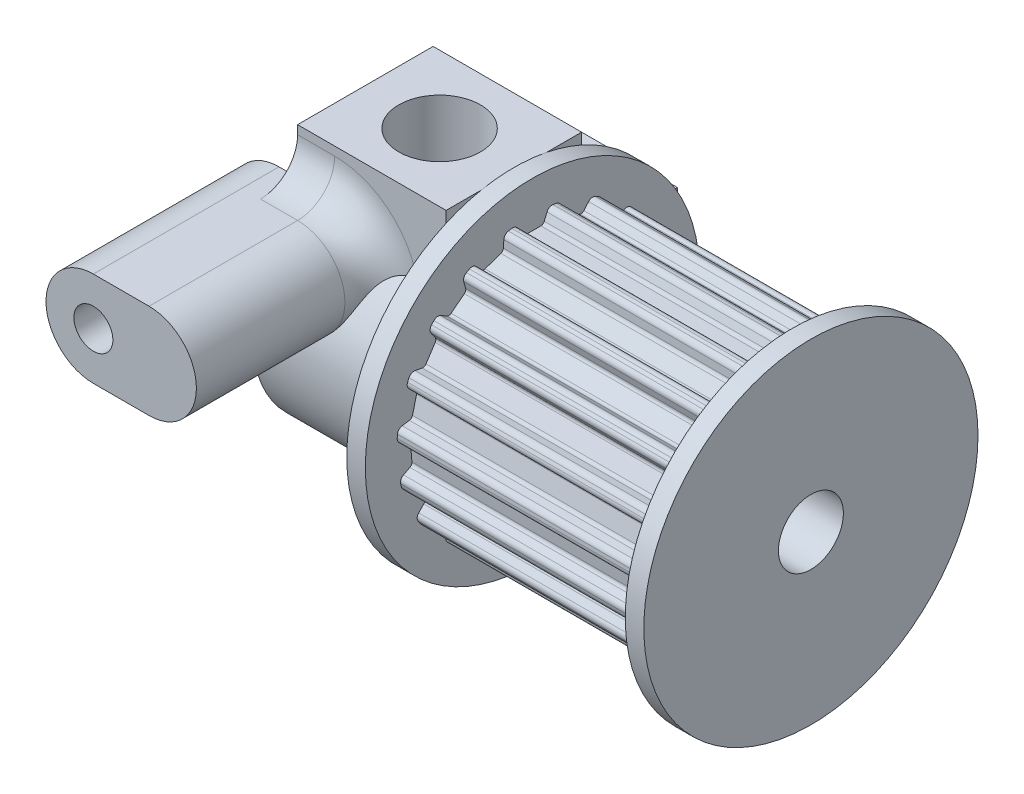
SolidWorks part; units mm, degrees
material "PLA Black"
ref_plane "Front" through (0, 0, 0) normal (0, 0, 1) x (1, 0, 0)
ref_plane "Top" through (0, 0, 0) normal (0, 1, 0) x (1, 0, 0)
ref_plane "Right" through (0, 0, 0) normal (1, 0, 0) x (0, 0, -1)
sketch "Sketch1" plane through (0, 0, 0) normal (1, 0, 0) x (0, 0, -1)
  line L0 (1.118, 1) -> (-1.118, 1) construction
  line L1 (-3.65, 4.8249) -> (3.65, 4.8249)
  line L2 (4.8249, 3.65) -> (4.8249, -3.65)
  line L3 (0, 0) -> (11.6334, 0) construction
  line L4 (0, 0) -> (0, 8.6732) construction
  arc A0 (-1.118, 1) -> (1.118, 1) centre (0, 0) ccw construction
  circle A1 centre (0, 0) radius 1.75
  arc A2 (4.8249, -3.65) -> (-3.65, 4.8249) centre (0, 0) cw
  arc A3 (4.8249, 3.65) -> (3.65, 4.8249) centre (0, 0) ccw
  dimension "D1" = 3
  dimension "D3" = 0.25
  dimension "D5" = 6.05
  dimension "D2" = 1
  dimension "D4" = 7.3
extrude "Boss-Extrude1" add sketch "Sketch1" along normal mid plane 8
sketch "Sketch2" plane through (0, 4.8249, 0) normal (0, 1, 0) x (1, 0, 0)
  circle A0 centre (0, 0) radius 2.2
  dimension "D1" = 4.4
extrude "Cut-Extrude1" cut sketch "Sketch2" against normal blind 5
sketch "Sketch7" plane through (4, 0, 0) normal (1, 0, 0) x (0, 0, -1)
  circle A0 centre (0, 0) radius 1.75 construction
  circle A1 centre (0, 0) radius 7.3
  circle A2 centre (0, 0) radius 1.75
  dimension "D1" = 14.6
extrude "Boss-Extrude5" add sketch "Sketch7" along normal blind 15
sketch "Sketch8" plane through (19, 0, 0) normal (1, 0, 0) x (0, 0, -1)
  line L0 (-0.4541, 6.5499) -> (0.4528, 6.5499)
  line L1 (0.6374, 6.6734) -> (0.7865, 7.0333)
  line L2 (-0.6389, 6.6734) -> (-0.788, 7.0333)
  line L6 (0, 9.2013) -> (0, 0) construction
  arc A0 (0.4528, 6.5499) -> (0.6374, 6.6734) centre (0.4526, 6.7499) ccw
  arc A1 (-0.4541, 6.5499) -> (-0.6389, 6.6734) centre (-0.4541, 6.7499) cw
  arc A2 (0.7865, 7.0333) -> (1.1093, 7.2152) centre (1.0638, 6.9187) cw
  arc A3 (-0.788, 7.0333) -> (-1.1108, 7.215) centre (-1.0652, 6.9185) ccw
  circle A4 centre (0, 0) radius 7.3 construction
  arc A5 (-1.1108, 7.215) -> (1.1093, 7.2152) centre (0, 0) cw
  point P3 (-0.0007, 6.5499)
  point P15 (0, 9.84)
extrude "Cut-Extrude3" cut sketch "Sketch8" against normal up to surface (15 mm away) up to face at (4, 0, -7.3)
pattern_circular "CirPattern1" count 19 over 360 about axis through (19, 0, 0) along (-1, 0, 0) of "Cut-Extrude3"
sketch "Sketch9" plane through (19, 0, 0) normal (1, 0, 0) x (0, 0, -1)
  circle A0 centre (0, 0) radius 9
  circle A1 centre (0, 0) radius 1.75 construction
  circle A2 centre (0, 0) radius 1.75
  dimension "D1" = 18
extrude "Boss-Extrude6" add sketch "Sketch9" along normal blind 1
sketch "Sketch10" plane through (4, 0, 0) normal (-1, 0, 0) x (0, 0, 1)
  circle A0 centre (0, 0) radius 9
  circle A1 centre (0, 0) radius 9 construction
  circle A2 centre (0, 0) radius 1.75 construction
  circle A3 centre (0, 0) radius 1.75
extrude "Boss-Extrude7" add sketch "Sketch10" against normal blind 1
sketch "Sketch3" plane through (0, 0, -4.8249) normal (0, 0, -1) x (-1, 0, 0)
  circle A0 centre (0, 0) radius 2.2
  dimension "D1" = 4.4
extrude "Cut-Extrude2" cut sketch "Sketch3" against normal blind 5
sketch "Sketch4" plane through (0, 4.8249, 0) normal (0, 1, 0) x (1, 0, 0)
  line L0 (4, 3.65) -> (-4, 3.65) construction
  line L2 (4, -3.65) -> (-4, -3.65) construction
  line L3 (-4, 3.65) -> (-4, -3.65) construction
  line L4 (4, 3.65) -> (-4, 3.65)
  line L5 (4, 3.65) -> (4, -3.65)
  line L6 (4, -3.65) -> (-4, -3.65)
  line L7 (-4, 3.65) -> (-4, -3.65)
  line L8 (4, 7.3) -> (4, -7.3) construction
  circle A0 centre (0, 0) radius 2.2 construction
  circle A1 centre (0, 0) radius 2.2
extrude "Boss-Extrude2" add sketch "Sketch4" along normal blind 4
sketch "Sketch5" plane through (0, 0, -4.8249) normal (0, 0, -1) x (-1, 0, 0)
  line L0 (-4, 3.65) -> (4, 3.65) construction
  line L1 (4, -3.65) -> (4, 3.65) construction
  line L2 (-4, -3.65) -> (4, -3.65) construction
  line L4 (-4, 3.65) -> (4, 3.65)
  line L5 (4, -3.65) -> (4, 3.65)
  line L6 (-4, -3.65) -> (4, -3.65)
  line L7 (-4, -3.65) -> (-4, 3.65)
  line L8 (-4, -7.3) -> (-4, 7.3) construction
  circle A0 centre (0, 0) radius 2.2 construction
  circle A1 centre (0, 0) radius 2.2
extrude "Boss-Extrude3" add sketch "Sketch5" along normal blind 4
ref_axis "Axis1" through (20, 0, 0) along (-1, 0, 0)
sketch "Sketch6" plane through (0, 0, 3.65) normal (0, 0, 1) x (1, 0, 0)
  line L0 (-4, 8.8249) -> (-4, 4.8249) construction
  line L2 (-2, 6.3555) -> (-5, 6.3555)
  line L3 (-5, 1.2545) -> (-2, 1.2545)
  line L6 (20, 0) -> (-4, 0) construction
  circle A0 centre (-5, 3.805) radius 1.0505
  arc A1 (-5, 6.3555) -> (-5, 1.2545) centre (-5, 3.805) ccw
  arc A2 (-2, 6.3555) -> (-2, 1.2545) centre (-2, 3.805) cw
  dimension "D1" = 2.101
  dimension "D2" = 3.805
  dimension "D3" = 1.5
  dimension "D4" = 1
  dimension "D5" = 3
extrude "Boss-Extrude4" add sketch "Sketch6" along normal blind 10
fillet "Fillet1" radius 2 2 edges at (-0.6029, 5.9388, 3.65) (-3, 6.3555, 3.65)
equation "\"knee_angle\"= 70"
equation "\"ankle_angle\" = 80"
equation "\"hip_angle\" = 40"
equation "\"spring_ankle_parallel_arm_diameter\"= 1.1"
equation "\"spring_ankle_parallel_arm_length\"= 13"
equation "\"spring_ankle_parallel_intern_diameter\"= 5.7"
equation "\"spring_ankle_parallel_angle\"= \"ankle_angle\""
equation "\"spring_ankle_parallel_turns\"= 3"
equation "\"spring_ankle_parallel_pitch\"= \"spring_ankle_parallel_arm_diameter\" * 1.01"
equation "\"spring_ankle_parallel_cutting_distance\"= (1-\"spring_ankle_parallel_angle\" / 360) * \"spring_ankle_parallel_pitch\""
equation "\"spring_ankle_serial_arm_diameter\"= 1.91"
equation "\"spring_ankle_serial_arm_length\"= 10"
equation "\"spring_ankle_serial_intern_diameter\"= 5.7"
equation "\"spring_ankle_serial_angle\"= \"90\""
equation "\"spring_ankle_serial_turns\"= 3"
equation "\"spring_ankle_serial_pitch\"= \"spring_ankle_serial_arm_diameter\" * 1.01"
equation "\"spring_ankle_serial_cutting_distance\"= (1-\"spring_ankle_serial_angle\" / 360) * \"spring_ankle_serial_pitch\""
equation "\"spring_knee_parallel_arm_diameter\"= 1.1"
equation "\"spring_knee_parallel_arm_length\"= 13"
equation "\"spring_knee_parallel_intern_diameter\"= 5.7"
equation "\"spring_knee_parallel_angle\"= -\"knee_angle\" + 90"
equation "\"spring_knee_parallel_turns\"= 3"
equation "\"spring_knee_parallel_pitch\"= \"spring_knee_parallel_arm_diameter\" * 1.01"
equation "\"spring_knee_parallel_cutting_distance\"= (1-(\"spring_knee_parallel_angle\") / 360) * \"spring_knee_parallel_pitch\""
equation "\"spring_knee_serial_arm_diameter\"= 1.91"
equation "\"spring_knee_serial_arm_length\"= 10"
equation "\"spring_knee_serial_intern_diameter\"= 5.7"
equation "\"spring_knee_serial_angle\"= \"90\""
equation "\"spring_knee_serial_turns\"= 3"
equation "\"spring_knee_serial_pitch\"= \"spring_knee_serial_arm_diameter\" * 1.01"
equation "\"spring_knee_serial_cutting_distance\"= (1-\"spring_knee_serial_angle\" / 360) * \"spring_knee_serial_pitch\""
equation "\"D2@Sketch6\" = ( \"spring_ankle_serial_intern_diameter\" + \"spring_ankle_serial_arm_diameter\" ) / 2"
equation "\"D1@Sketch6\" = \"spring_ankle_serial_arm_diameter\" * 1.1"
